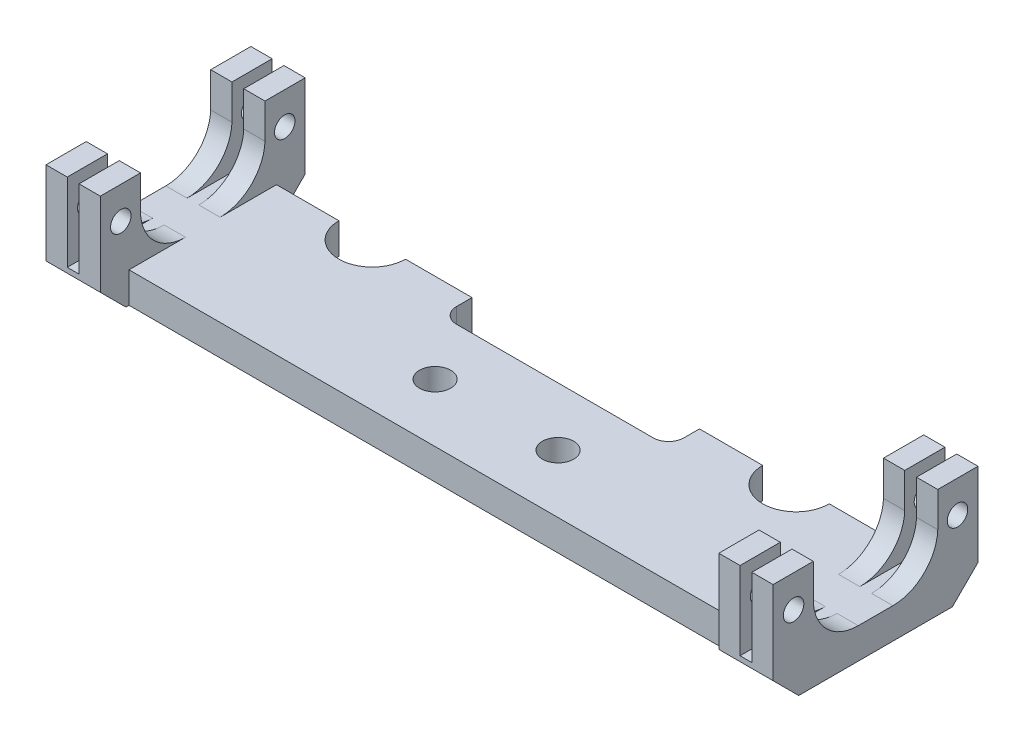
SolidWorks part; units mm, degrees
ref_plane "Front Plane" through (0, 0, 0) normal (0, 0, 1) x (1, 0, 0)
ref_plane "Top Plane" through (0, 0, 0) normal (0, 1, 0) x (1, 0, 0)
ref_plane "Right Plane" through (0, 0, 0) normal (1, 0, 0) x (0, 0, -1)
sketch "Sketch1" plane through (0, 0, 0) normal (0, 1, 0) x (1, 0, 0)
  line L0 (-26.8834, 0) -> (-26.8834, 14.3966)
  line L1 (-26.8834, 14.3966) -> (-24.0934, 14.3966)
  line L2 (0, 24.3967) -> (0, -4.386) construction
  line L3 (-17.5934, 14.3966) -> (0, 14.3966)
  line L4 (-26.8834, 0) -> (0, 0)
  line L5 (0, 14.3966) -> (0, 0)
  arc A1 (-24.0934, 14.3966) -> (-17.5934, 14.3966) centre (-20.8434, 14.3966) ccw
  dimension "D2" = 6.5
extrude "Boss-Extrude1" add sketch "Sketch1" along normal blind 3
sketch "Sketch2" plane through (-26.8834, 0, 0) normal (-1, 0, 0) x (0, 0, 1)
  line L4 (-14.3966, 0) -> (0, 0)
  line L5 (0, 0) -> (0, 3)
  line L6 (0, 3) -> (-14.3966, 3)
  line L7 (-14.3966, 3) -> (-14.3966, 0)
  line L8 (-14.3966, 0) -> (0, 0)
  line L9 (0, 0) -> (0, 3)
  line L10 (0, 3) -> (-14.3966, 3)
  line L11 (-14.3966, 3) -> (-14.3966, 0)
  dimension "D1" = 0
extrude "Boss-Extrude2" add sketch "Sketch2" along normal blind 8.6
sketch "Sketch3" plane through (-35.4834, 0, 0) normal (-1, 0, 0) x (0, 0, 1)
  line L4 (0, 3) -> (-14.3966, 3) construction
  line L7 (1.5328, 10.6321) -> (-1.1233, 10.6321)
  line L10 (-13.2733, 10.6321) -> (-15.9294, 10.6321)
  line L11 (-13.2733, 7.2303) -> (-13.2733, 10.5571)
  line L15 (-1.1233, 7.5478) -> (-1.1233, 10.5571)
  line L16 (-8.8878, 3) -> (-5.5088, 3)
  line L17 (-13.2733, 10.5571) -> (-15.8975, 10.5571) construction
  line L18 (-12.6983, 3.075) -> (-1.6983, 3.075) construction
  line L19 (1.5009, 10.5571) -> (-1.1233, 10.5571) construction
  line L20 (-1.1233, 10.5571) -> (-1.1233, 10.6321)
  line L21 (-13.2733, 10.5571) -> (-13.2733, 10.6321)
  line L22 (-13.1983, 10.6321) -> (-15.9294, 10.6321) construction
  line L23 (-13.1983, 7.2316) -> (-13.1983, 10.6321) construction
  line L24 (-8.8878, 3.075) -> (-5.5088, 3.075) construction
  line L25 (-1.1983, 7.5464) -> (-1.1983, 10.6321) construction
  line L26 (1.5328, 10.6321) -> (-1.1983, 10.6321) construction
  line L27 (2.8017, 7.5) -> (2.8017, 0)
  line L28 (2.8017, 0) -> (0, 0)
  line L29 (-17.1983, 7.5) -> (-17.1983, 0)
  line L30 (-17.1983, 0) -> (-14.3966, 0)
  line L31 (-17.1983, 7.5) -> (-17.1983, 10.6321)
  line L32 (-17.1983, 10.6321) -> (-15.9294, 10.6321)
  line L33 (1.5328, 10.6321) -> (2.8017, 10.6321)
  line L34 (2.8017, 10.6321) -> (2.8017, 7.5)
  line L35 (-14.3966, 0) -> (0, 0)
  line L37 (-12.6983, 3) -> (-1.6983, 3) construction
  circle A4 centre (-15.1983, 7.5) radius 1
  circle A5 centre (0.8017, 7.5) radius 1
  arc A8 (-5.5088, 3) -> (-1.1233, 7.5478) centre (-5.5088, 7.3884) ccw
  arc A9 (-13.2733, 7.2303) -> (-8.8878, 3) centre (-8.8878, 7.3884) ccw
  arc A10 (-15.8975, 10.5571) -> (-12.6983, 3.075) centre (-12.6983, 7.5) ccw construction
  arc A11 (-1.6983, 3.075) -> (1.5009, 10.5571) centre (-1.6983, 7.5) ccw construction
  arc A12 (-13.1983, 7.2316) -> (-8.8878, 3.075) centre (-8.8878, 7.3884) ccw construction
  arc A13 (-5.5088, 3.075) -> (-1.1983, 7.5464) centre (-5.5088, 7.3884) ccw construction
  arc A14 (-15.9294, 10.6321) -> (-12.6983, 3) centre (-12.6983, 7.5) ccw construction
  arc A15 (-1.6983, 3) -> (1.5328, 10.6321) centre (-1.6983, 7.5) ccw construction
  point P8 (-7.1983, 3)
  line M7 (-14.3966, 3) -> (-14.3966, 0)
  line M9 (0, 0) -> (0, 3)
  line M10 (0, 3) -> (-14.3966, 3)
  dimension "D1" = 16
  dimension "D2" = 8
  dimension "D3" = 0.075
extrude "Boss-Extrude3" add sketch "Sketch3" against normal blind 5.3 contours A9 L11 L21 L10 L32 L31 L29 L30 L28 L27 L34 L33 L7 L20 L15 A8 L16 A5 A4 M7 M10 M9 | A8 L28 L27 L34 L33 L7 L20 L15 A5 M10 M9 region at (-35.4834, 5.3282, 0.654) region at (-35.4834, 5.3283, -15.0505)
sketch "Sketch4" plane through (0, 0, 2.8017) normal (0, 0, 1) x (1, 0, 0)
  line L0 (-30.1834, 10.6321) -> (-35.4834, 10.6321) construction
  line L1 (-33.4084, 10.6321) -> (-32.2584, 10.6321)
  line L2 (-33.4084, 10.6321) -> (-33.4084, 3)
  line L3 (-33.4084, 3) -> (-32.2584, 3)
  line L4 (-32.2584, 10.6321) -> (-32.2584, 3)
  line L5 (-30.1834, 3) -> (0, 3) construction
  point P6 (-32.8334, 10.6321)
  point P7 (-32.8334, 10.6321)
  dimension "D1" = 1.15
extrude "Cut-Extrude1" cut sketch "Sketch4" against normal blind 26.3
chamfer "Chamfer1" distance 2.5 angle 45 2 edges at (-32.8334, 0, 2.8017) (-32.8334, 0, -17.1983)
sketch "Sketch5" plane through (0, 3, 0) normal (0, 1, 0) x (1, 0, 0)
  line L0 (0, 11.3812) -> (-9.599, 11.3812)
  line L1 (-11.099, 12.8812) -> (-11.099, 14.3966)
  line L2 (-11.099, 14.3966) -> (0, 14.3966)
  line L3 (0, 14.3966) -> (0, 11.3812)
  line L4 (0, 14.3966) -> (-17.5934, 14.3966) construction
  arc A0 (-9.599, 11.3812) -> (-11.099, 12.8812) centre (-9.599, 12.8812) cw
  dimension "D1" = 1.5
extrude "Cut-Extrude2" cut sketch "Sketch5" against normal blind 10
mirror "Mirror1" about plane through (0, 0, 0) normal (1, 0, 0) of "Chamfer1", "Boss-Extrude2", "Boss-Extrude1", "Boss-Extrude3", "Cut-Extrude1", "Cut-Extrude2"
sketch "Sketch6" plane through (0, 3, 0) normal (0, 1, 0) x (1, 0, 0)
  line L0 (23.7734, 14.3966) -> (25.8173, 14.3966)
  line L1 (24.0934, 14.3966) -> (30.1834, 14.3966) construction
  line L2 (25.8173, 14.3966) -> (25.8173, 11.1466)
  line L3 (25.8173, 11.1466) -> (20.8434, 11.1466)
  circle A0 centre (20.5234, 14.3966) radius 3.25
  arc A1 (17.5934, 14.3966) -> (24.0934, 14.3966) centre (20.8434, 14.3966) ccw construction
  arc M37 (24.0934, 14.3966) -> (17.5934, 14.3966) centre (20.8434, 14.3966) cw
  line M38 (17.5934, 14.3966) -> (11.099, 14.3966)
  dimension "D2" = 6.5
  dimension "D1" = 0.32
extrude "Cut-Extrude5" cut sketch "Sketch6" against normal blind 10 contours A0 M38 M37 region at (17.4334, 3, -14.3495)
extrude "Boss-Extrude4" add sketch "Sketch6<3>" against normal through all contours A0 L0 M37 region at (23.9334, 3, -14.3495)
sketch "Sketch6<3>" plane through (0, 3, 0) normal (0, 1, 0) x (1, 0, 0) same geometry as "Sketch6"
sketch "Sketch7" plane through (0, 3, 0) normal (0, 1, 0) x (1, 0, 0)
  line L0 (0, 0) -> (0, 11.3812) construction
  line L1 (-30.1834, 0) -> (30.1834, 0) construction
  line L2 (-9.599, 11.3812) -> (9.599, 11.3812) construction
  circle A0 centre (-6, 5.6906) radius 1.525
  circle A1 centre (6, 5.6906) radius 1.525
  point P9 (0, 5.6906)
  dimension "D2" = 3.05
  dimension "D1" = 6
extrude "Cut-Extrude6" cut sketch "Sketch7" against normal through all
sketch "Sketch8" plane through (-35.4834, 0, 0) normal (-1, 0, 0) x (0, 0, 1)
  line L10 (-14.6983, 0) -> (0.3017, 0)
  line L11 (0.3017, 0) -> (2.8017, 2.5)
  line L12 (2.8017, 2.5) -> (2.8017, 10.6321)
  line L13 (2.8017, 10.6321) -> (-1.1233, 10.6321)
  line L14 (-1.1233, 10.6321) -> (-1.1233, 7.5478)
  line L15 (-5.5088, 3) -> (-8.8878, 3)
  line L16 (-13.2733, 7.2303) -> (-13.2733, 10.6321)
  line L17 (-13.2733, 10.6321) -> (-17.1983, 10.6321)
  line L18 (-17.1983, 10.6321) -> (-17.1983, 2.5)
  line L19 (-17.1983, 2.5) -> (-14.6983, 0)
  line L20 (-14.6983, 0) -> (0.3017, 0)
  line L21 (0.3017, 0) -> (2.8017, 2.5)
  line L22 (2.8017, 2.5) -> (2.8017, 10.6321)
  line L23 (2.8017, 10.6321) -> (-1.1233, 10.6321)
  line L24 (-1.1233, 10.6321) -> (-1.1233, 7.5478)
  line L25 (-5.5088, 3) -> (-8.8878, 3)
  line L26 (-13.2733, 7.2303) -> (-13.2733, 10.6321)
  line L27 (-13.2733, 10.6321) -> (-17.1983, 10.6321)
  line L28 (-17.1983, 10.6321) -> (-17.1983, 2.5)
  line L29 (-17.1983, 2.5) -> (-14.6983, 0)
  circle A0 centre (-15.1983, 7.5) radius 1
  circle A1 centre (0.8017, 7.5) radius 1
  arc A2 (-5.5088, 3) -> (-1.1233, 7.5478) centre (-5.5088, 7.3884) ccw
  arc A3 (-13.2733, 7.2303) -> (-8.8878, 3) centre (-8.8878, 7.3884) ccw
  arc A4 (-5.5088, 3) -> (-1.1233, 7.5478) centre (-5.5088, 7.3884) ccw
  arc A5 (-13.2733, 7.2303) -> (-8.8878, 3) centre (-8.8878, 7.3884) ccw
  dimension "D1" = 0
